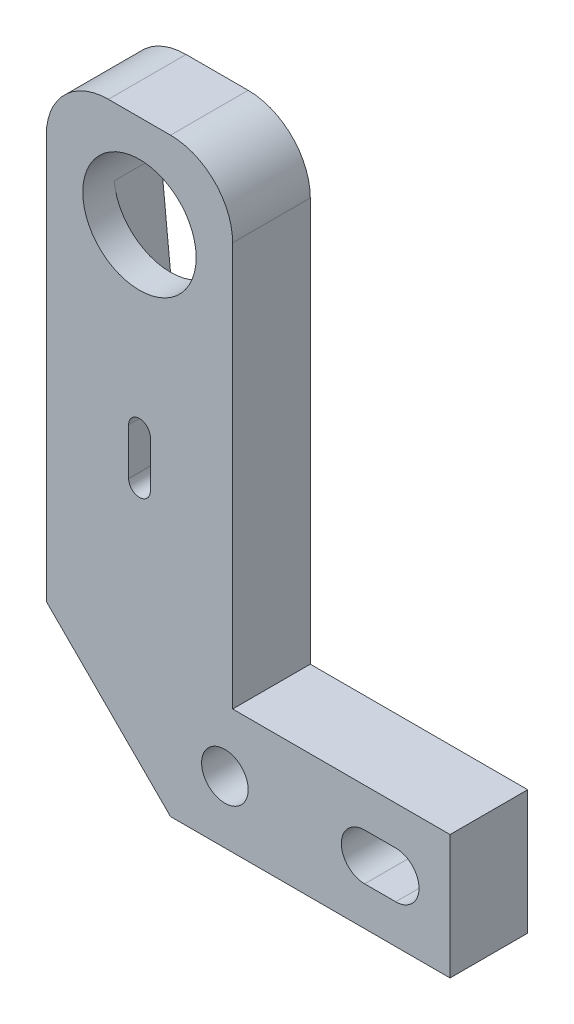
SolidWorks part; units mm, degrees
material "ABS"
ref_plane "Plano frontal" through (0, 0, 0) normal (0, 0, 1) x (1, 0, 0)
ref_plane "Plano superior" through (0, 0, 0) normal (0, 1, 0) x (1, 0, 0)
ref_plane "Plano direito" through (0, 0, 0) normal (1, 0, 0) x (0, 0, -1)
sketch "Esboço1" plane through (0, 0, 0) normal (0, 0, 1) x (1, 0, 0)
  line L0 (0, 0) -> (0, -24) construction
  line L1 (-6, 2) -> (-6, -24)
  line L2 (6, 2) -> (6, -24)
  line L3 (20, -32) -> (20, -24)
  line L4 (-6, -24) -> (2, -32)
  line L5 (2, -32) -> (20, -32)
  line L6 (20, -24) -> (6, -24)
  line L7 (5.5, -28) -> (16.5, -28) construction
  line L8 (-2, 6) -> (2, 6)
  line L9 (2.2387, -14.225) -> (3.6317, -0.365)
  line L10 (-3.6317, -0.365) -> (-2.2387, -14.225)
  line L11 (0, -14.5) -> (0, -11.5) construction
  line L12 (-0.7, -14.5) -> (-0.7, -11.5)
  line L13 (0.7, -14.5) -> (0.7, -11.5)
  line L14 (16.5, -26.5) -> (14.5, -26.5)
  line L15 (6, 0) -> (6, -24) construction
  line L16 (14.5, -29.5) -> (16.5, -29.5)
  line L17 (-6, 0) -> (-6, -24) construction
  circle A0 centre (5.5, -28) radius 1.5
  arc A1 (16.5, -29.5) -> (16.5, -26.5) centre (16.5, -28) ccw
  circle A2 centre (0, 0) radius 3.65
  arc A3 (-2.2387, -14.225) -> (2.2387, -14.225) centre (0, -14) ccw
  arc A4 (-0.7, -14.5) -> (0.7, -14.5) centre (0, -14.5) ccw
  arc A5 (0.7, -11.5) -> (-0.7, -11.5) centre (0, -11.5) ccw
  arc A6 (14.5, -26.5) -> (14.5, -29.5) centre (14.5, -28) ccw
  arc A7 (6, 2) -> (2, 6) centre (2, 2) ccw
  arc A8 (-6, 2) -> (-2, 6) centre (-2, 2) cw
  point P15 (-2, -28)
  point P25 (0, -13)
  point P36 (11, -28)
  point P37 (11, -32)
  point P45 (-6, 6)
  dimension "D3" = 3
  dimension "D8" = 7.3
  dimension "D11" = 4.5
  dimension "D12" = 0.7
  dimension "D16" = 4
  dimension "D4" = 8
  dimension "D6" = 18
  dimension "D7" = 30
  dimension "D9" = 6
  dimension "D10" = 14
  dimension "D13" = 3
  dimension "D14" = 0.5
  dimension "D15" = 2
  dimension "D5" = 8
  dimension "D17" = 8
  dimension "D1" = 6
  dimension "D2" = 6
extrude "Ressalto-extrusão1" add sketch "Esboço1" along normal blind 5 contours L8 L1 L4 L5 L2 A2 L9 A3 L10 A1 A0 | L0 A2 L10 A3 | A2 L0 A3 L9 region at (1.5336, -8.5081, 0) region at (-1.5336, -8.5081, 0) region at (3.3272, -17.5644, 0)
extrude "Corte-extrusão1" cut sketch "Esboço1<3>" along normal blind 3 contours L10 A3 L9 A2 A5 L13 A4 L12 region at (0, -8.5081, 0)
sketch "Esboço1<3>" plane through (0, 0, 0) normal (0, 0, 1) x (1, 0, 0) same geometry as "Esboço1"
equation "\"D2@Esboço1\"=\"D1@Esboço1\""
